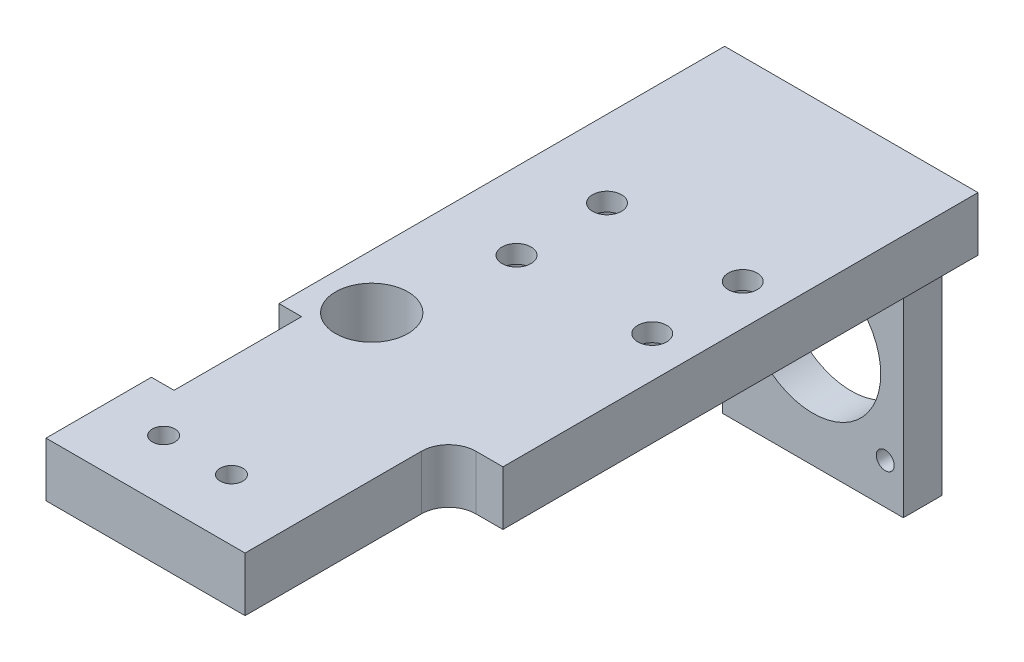
SolidWorks part; units mm, degrees
ref_plane "Top" through (0, 0, 0) normal (0, 0, 1) x (1, 0, 0)
ref_plane "Front" through (0, 0, 0) normal (0, 1, 0) x (1, 0, 0)
ref_plane "Right" through (0, 0, 0) normal (1, 0, 0) x (0, 0, -1)
sketch "Back Sketch" plane through (0, 0, 0) normal (0, 1, 0) x (1, 0, 0)
  line L0 (-14, 0) -> (14, 0) construction
  line L1 (14, 4.25) -> (14, -48.25)
  line L2 (14, -48.25) -> (11, -48.25)
  line L3 (8, -51.25) -> (8, -70.75)
  line L4 (8, -70.75) -> (-14, -70.75)
  line L5 (-14, -70.75) -> (-14, -59.1)
  line L6 (-14, 4.25) -> (14, 4.25)
  line L7 (-14, -59.1) -> (-11.5, -59.1)
  line L8 (-11.5, -59.1) -> (-11.5, -45)
  line L9 (-11.5, -45) -> (-14, -45)
  line L10 (-14, -45) -> (-14, 4.25)
  arc A0 (8, -51.25) -> (11, -48.25) centre (11, -51.25) cw
  circle A1 centre (9.5, -17.25) radius 0.8
  circle A2 centre (-5.5, -17.25) radius 0.8
  circle A3 centre (-5.5, -27.25) radius 0.8
  circle A4 centre (9.5, -27.25) radius 0.8
  circle A5 centre (-8, -40.75) radius 4
  circle A6 centre (-7.75, -64) radius 1.25
  circle A7 centre (-0.25, -64) radius 1.25
  point P8 (12.5, -48.25)
  point P30 (0, 0)
  point P31 (0, 0)
  dimension "D1" = 3
  dimension "D8" = 1.6
  dimension "D14" = 8
  dimension "D17" = 2.5
  dimension "D2" = 6
  dimension "D3" = 28
  dimension "D5" = 22.5
  dimension "D6" = 4.25
  dimension "D7" = 21.5
  dimension "D4" = 75
  dimension "D9" = 10
  dimension "D10" = 15
  dimension "D12" = 14.1
  dimension "D13" = 2.5
  dimension "D15" = 30
  dimension "D16" = 6
  dimension "D18" = 7.5
  dimension "D19" = 6.25
  dimension "D20" = 6.75
  dimension "D21" = 4.5
  dimension "D11" = 45
extrude "Back Extrude" add sketch "Back Sketch" along normal blind 6
sketch "Bottom Sketch" plane through (0, 0, 0) normal (0, 0, 1) x (1, 0, 0)
  line L0 (-10, -25) -> (-10, 0)
  line L1 (-14, 0) -> (14, 0)
  line L2 (-14, 0) -> (-14, -25) construction
  line L3 (-14, -25) -> (14, -25)
  line L4 (14, 0) -> (14, -25) construction
  line L5 (10, -25) -> (10, 0)
  line L7 (-10, 0) -> (10, -25) construction
  circle A0 centre (0, -12.5) radius 7.5
  circle A1 centre (-8, -4.5) radius 0.9899
  circle A2 centre (8, -4.5) radius 0.9899
  circle A3 centre (8, -20.5) radius 0.9899
  circle A4 centre (-8, -20.5) radius 0.9899
  dimension "D7" = 15
  dimension "D1" = 28
  dimension "D3" = 16
  dimension "D4" = 16
  dimension "D5" = 8
  dimension "D6" = 8
  dimension "D8" = 25
  dimension "D2" = 20
extrude "Bottom Extrude" add sketch "Bottom Sketch" against normal blind 4.25 separate body contours L3 L5 L1 L0 A4 A3 A2 A1 A0 region at (-9.6798, -12.5, 0)
hole_wizard "Carraige Mount  M3s" positions "3DSketch1" profile "Sketch1" counterbore size "M3" standard "ANSI Metric" end condition through all
sketch3d "3DSketch1"
  point P1 (9.5, 0, 27.25)
  point P3 (-5.5, 0, 27.25)
  point P5 (-5.5, 0, 17.25)
  point P7 (9.5, 0, 17.25)
  point P10 (0, 0, 0)
  point P11 (0, 0, 0)
  point P13 (0, 0, 0)
  point P15 (0, 0, 0)
  point P17 (0, 0, 0)
sketch "Sketch1" plane through (9.5, 0, 27.25) normal (1, 0, 0) x (0, 0, -1)
  line L0 (0, 0) -> (0, 6)
  line L1 (0, 6) -> (1.6, 6)
  line L3 (1.6, 6) -> (1.6, 4)
  line L4 (1.6, 4) -> (3.25, 4)
  line L5 (3.25, 4) -> (3.25, 0)
  line L7 (3.25, 0) -> (0, 0)
  line L11 (0, -6.35) -> (0, 107.95) construction
  dimension "Thru Hole Dia." = 3.2
  dimension "Thru Hole Depth" = 6
  dimension "C'Bore Dia." = 6.5
  dimension "C'Bore Depth" = 4
hole_wizard "Rotational Sensor Tapped Holes M2.5x0.45 Tapped Holes" positions "Sketch3" profile "Sketch4" tap size "M2.5x0.45" standard "ANSI Metric"
sketch "Sketch3" plane through (-11.5, 0, 0) normal (-1, 0, 0) x (0, 0, 1)
  point P0 (55.25, 3.25)
  point P2 (48.25, 3.25)
  point P6 (0, 0)
  point P7 (0, 0)
  point P8 (0, 0)
  point P9 (0, 0)
  point P10 (0, 0)
  dimension "D1" = 3.25
  dimension "D2" = 48.25
  dimension "D3" = 7
sketch "Sketch4" plane through (-11.5, 3.25, 55.25) normal (0, 1, 0) x (0, 0, 1)
  line L0 (0, 0) -> (0, 4.6159)
  line L1 (0, 4.6159) -> (1.025, 4)
  line L2 (1.025, 4) -> (1.025, 0)
  line L5 (1.025, 0) -> (0, 0)
  line L10 (0, 4.6159) -> (-1.025, 4) construction
  line L11 (0, -6.35) -> (0, 107.95) construction
  dimension "Tap Drill Dia." = 2.05
  dimension "Tap Drill Depth" = 4
  dimension "Drill Angle" = 118
cosmetic thread "Hole Thread1" parameters "D1"=4, "D2"=2.5
cosmetic thread "Hole Thread3" parameters "D1"=4, "D2"=2.5
equation "\"M2 Close Fit Hole\"= 2.2"
equation "\"M2.5 Close Fit Hole\"= 2.7"
equation "\"M3 Close Fit Hole\"= 3.2"
equation "\"M4 Close Fit Hole\"= 4.3"
equation "\"M5 Close Fit Hole\"= 5.3"
equation "\"M6 Close Fit Hole\"= 6.3"
equation "\"M7 Close Fit Hole\"= 7.4"
equation "\"M8 Close Fit Hole\"= 8.4"
equation "\"M2 Tap Hole 75%\"= 1.6"
equation "\"M3 Tap Hole 75%\"= 2.5"
equation "\"M4 Tap Hole 75%\"= 3.3"
equation "\"M5 Tap Hole 75%\"= 4.2"
equation "\"M6 Tap Hole 75%\"= 5"
equation "\"M7 Tap Hole 75%\"= 6"
equation "\"M8 Tap Hole 75%\"= 6.8"
equation "\"Bracket Width\"= 28mm"
equation "\"D1@Bottom Sketch\" = \"Bracket Width\""
equation "\"Bottom Thickness\"= 4.25"
equation "\"D1@Bottom Extrude\"=\"Bottom Thickness\""
equation "\"D6@Back Sketch\" = \"Bottom Thickness\""
equation "\"D8@Back Sketch\" = \"M2 Tap Hole 75%\""
equation "\"D17@Back Sketch\"=\"M3 Tap Hole 75%\""
equation "\"D3@Back Sketch\"=\"Bracket Width\""
